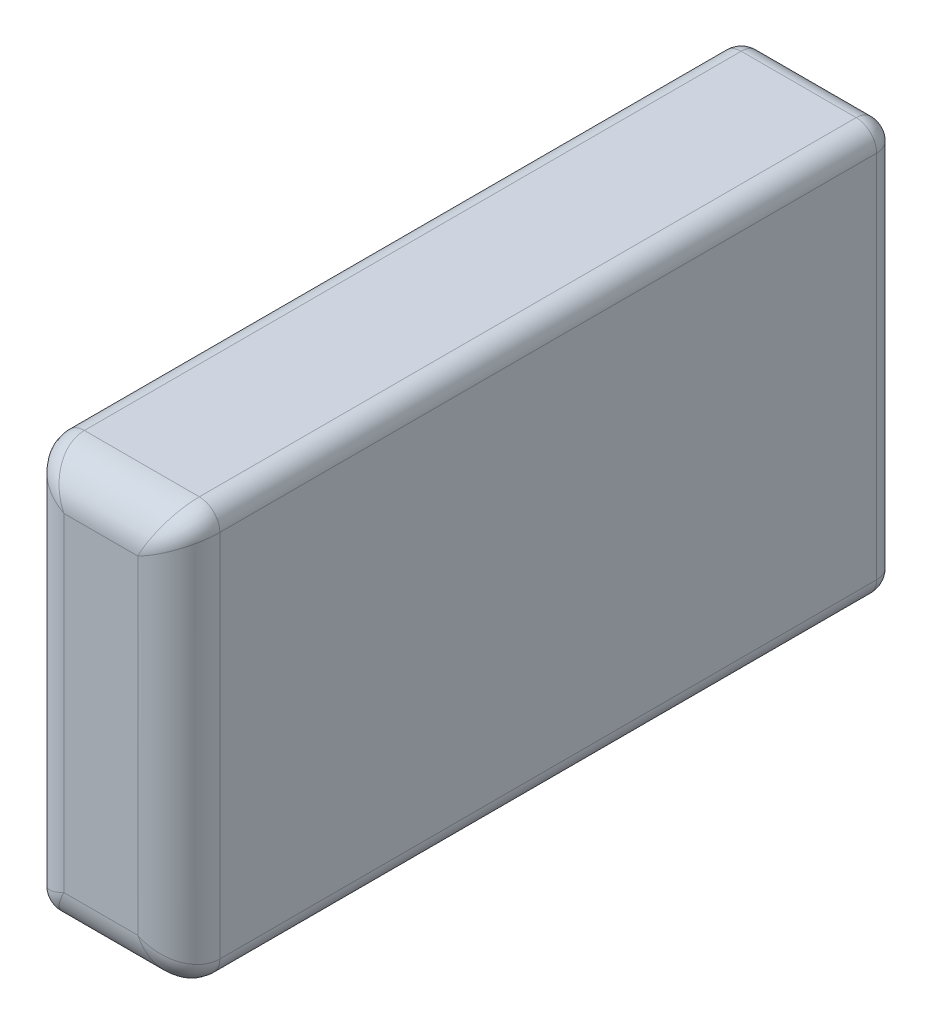
SolidWorks part; units mm, degrees
ref_plane "Front Plane" through (0, 0, 0) normal (1, 0, 0) x (0, 1, 0)
ref_plane "Top Plane" through (0, 0, 0) normal (0, 0, 1) x (0, 1, 0)
ref_plane "Right Plane" through (0, 0, 0) normal (0, 1, 0) x (-1, 0, 0)
sketch "Sketch1" plane through (0, 0, 0) normal (1, 0, 0) x (0, 1, 0)
  line L1 (0, 0) -> (25.4, 0)
  line L2 (0, 0) -> (0, 44.45)
  line L3 (0, 44.45) -> (25.4, 44.45)
  line L4 (25.4, 0) -> (25.4, 44.45)
  dimension "D1" = 25.4
  dimension "D2" = 44.45
extrude "Boss-Extrude1" add sketch "Sketch1" along normal blind 9.652
fillet "Fillet1" radius 1.27 4 edges at (0, 0, 22.225) (9.652, 0, 22.225) (0, 25.4, 22.225) (9.652, 25.4, 22.225)
fillet "Fillet2" radius 1.27 8 edges at (9.28, 0.372, 0) (9.652, 12.7, 0) (9.28, 25.028, 0) (4.826, 25.4, 0) (0.372, 25.028, 0) (0, 12.7, 0) (0.372, 0.372, 0) (4.826, 0, 0)
fillet "Fillet3" radius 2.54 8 edges at (0.372, 25.028, 44.45) (4.826, 25.4, 44.45) (9.28, 25.028, 44.45) (9.652, 12.7, 44.45) (9.28, 0.372, 44.45) (4.826, 0, 44.45) (0.372, 0.372, 44.45) (0, 12.7, 44.45)
